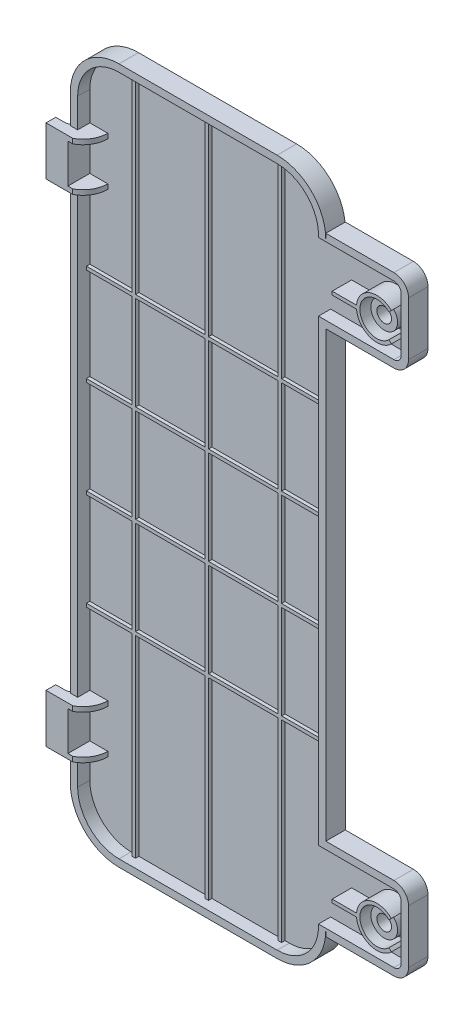
SolidWorks part; units mm, degrees
ref_plane "정면" through (0, 0, 0) normal (1, 0, 0) x (0, 1, 0)
ref_plane "윗면" through (0, 0, 0) normal (0, 0, 1) x (0, 1, 0)
ref_plane "우측면" through (0, 0, 0) normal (0, 1, 0) x (-1, 0, 0)
sketch "스케치1" plane through (0, 0, 0) normal (0, 0, 1) x (0, 1, 0)
  line L0 (-62.6, -26.25) -> (-62.6, -40.25)
  line L1 (-61.5, 26.25) -> (61.5, 26.25)
  line L2 (-71.5, 16.25) -> (-71.5, -16.25)
  line L3 (-61.5, -26.25) -> (-62.6, -26.25)
  line L4 (71.5, 16.25) -> (71.5, -16.25)
  line L5 (-71.5, 26.25) -> (0, 0) construction
  line L6 (-71.5, -26.25) -> (-48.7665, -17.9038) construction
  line L9 (-59.6, -43.25) -> (-48.6, -43.25)
  line L11 (-45.1107, -16.5616) -> (-40.2665, -26.25) construction
  line L12 (62.6, -26.25) -> (61.5, -26.25)
  line L15 (48.6, -43.25) -> (59.6, -43.25)
  line L17 (-45.6, -26.25) -> (45.6, -26.25)
  line L18 (0, 39.705) -> (0, -47.5697) construction
  line L19 (0, 0) -> (71.5, 26.25) construction
  line L20 (45.6, -26.25) -> (45.6, -40.25)
  line L21 (-45.6, -26.25) -> (-45.6, -40.25)
  line L24 (62.6, -26.25) -> (62.6, -40.25)
  line L25 (67.0036, -24.5992) -> (71.5, -26.25) construction
  arc A0 (61.5, 26.25) -> (71.5, 16.25) centre (61.5, 16.25) cw
  arc A1 (61.5, -26.25) -> (71.5, -16.25) centre (61.5, -16.25) ccw
  arc A2 (-71.5, -16.25) -> (-61.5, -26.25) centre (-61.5, -16.25) ccw
  arc A3 (-61.5, 26.25) -> (-71.5, 16.25) centre (-61.5, 16.25) ccw
  arc A4 (59.6, -43.25) -> (62.6, -40.25) centre (59.6, -40.25) ccw
  arc A5 (45.6, -40.25) -> (48.6, -43.25) centre (48.6, -40.25) ccw
  arc A6 (-48.6, -43.25) -> (-45.6, -40.25) centre (-48.6, -40.25) ccw
  arc A7 (-62.6, -40.25) -> (-59.6, -43.25) centre (-59.6, -40.25) ccw
  point P0 (0, 0)
  point P18 (-40.2665, -26.25)
  point P23 (45.1042, -26.25)
  point P27 (62.6, -43.25)
  point P36 (45.6, -43.25)
  point P41 (-45.6, -43.25)
  point P44 (-62.6, -43.25)
  point P47 (-45.6, -33.25)
  dimension "D3" = 10
  dimension "D8" = 3
  dimension "D1" = 143
  dimension "D2" = 52.5
  dimension "D4" = 17
  dimension "D5" = 17
  dimension "D6" = 17
  dimension "D7" = 17
  dimension "D9" = 45.6
  dimension "D10" = 45.6
extrude "보스-돌출1" add sketch "스케치1" along normal blind 4
shell "쉘1" thickness 1.5 removed face at (22.0743, 0, 4)
sketch "스케치2" plane through (0, 0, 0) normal (0, 0, -1) x (1, 0, 0)
  line L0 (43.25, 59.6) -> (43.25, 48.6) construction
  line L1 (43.25, -48.6) -> (43.25, -59.6) construction
  line L2 (26.25, 62.6) -> (40.25, 62.6) construction
  line L3 (40.25, -62.6) -> (26.25, -62.6) construction
  circle A0 centre (38.25, 54.1) radius 2.75
  circle A1 centre (38.25, -54.1) radius 2.75
  circle A2 centre (38.25, 54.1) radius 1.5
  circle A3 centre (38.25, -54.1) radius 1.5
  dimension "D1" = 5.5
  dimension "D2" = 5.5
  dimension "D3" = 5
  dimension "D4" = 5
  dimension "D5" = 8.5
  dimension "D6" = 8.5
extrude "보스-돌출2" add sketch "스케치2" against normal blind 4 contours A1 A3 | A0 A2 region at (35.5778, -54.1, 0) region at (35.5778, 54.1, 0)
sketch "스케치3" plane through (0, 0, 4) normal (0, 0, 1) x (1, 0, 0)
  line L1 (-24.75, 55.5) -> (-29.25, 55.5)
  line L2 (-24.75, 55.5) -> (-24.75, 45.5)
  line L3 (-24.75, 45.5) -> (-29.25, 45.5)
  line L4 (-29.25, 55.5) -> (-29.25, 45.5)
  line L6 (-24.75, -45.5) -> (-29.25, -45.5)
  line L7 (-24.75, -45.5) -> (-24.75, -55.5)
  line L8 (-24.75, -55.5) -> (-29.25, -55.5)
  line L9 (-29.25, -45.5) -> (-29.25, -55.5)
  line L11 (-24.75, 61.5) -> (-24.75, -61.5) construction
  line L12 (16.25, 71.5) -> (-16.25, 71.5) construction
  line L13 (-16.25, -71.5) -> (16.25, -71.5) construction
  point P10 (-27, -45.5)
  dimension "D1" = 10
  dimension "D2" = 10
  dimension "D3" = 4.5
  dimension "D4" = 4.5
  dimension "D5" = 0
  dimension "D6" = 0
  dimension "D7" = 91
  dimension "D8" = 143
  dimension "D9" = 16
extrude "보스-돌출3" add sketch "스케치3" along normal blind 2
fillet "필렛1" radius 1 2 edges at (-26.25, -50.5, 4) (-26.25, 50.5, 4)
sketch "스케치4" plane through (0, 0, 6) normal (0, 0, 1) x (1, 0, 0)
  line L1 (-24.75, 55.5) -> (-21.05, 55.5)
  line L2 (-24.75, 55.5) -> (-24.75, 54.5)
  line L3 (-24.75, 54.5) -> (-21.05, 54.5)
  line L4 (-21.05, 55.5) -> (-21.05, 54.5)
  line L5 (-24.75, 45.5) -> (-21.05, 45.5)
  line L6 (-24.75, 45.5) -> (-24.75, 46.5)
  line L7 (-24.75, 46.5) -> (-21.05, 46.5)
  line L8 (-21.05, 45.5) -> (-21.05, 46.5)
  line L9 (-24.75, -45.5) -> (-21.05, -45.5)
  line L10 (-24.75, -45.5) -> (-24.75, -46.5)
  line L11 (-24.75, -46.5) -> (-21.05, -46.5)
  line L12 (-21.05, -45.5) -> (-21.05, -46.5)
  line L13 (-24.75, -55.5) -> (-21.05, -55.5)
  line L14 (-24.75, -55.5) -> (-24.75, -54.5)
  line L15 (-24.75, -54.5) -> (-21.05, -54.5)
  line L16 (-21.05, -55.5) -> (-21.05, -54.5)
  dimension "D1" = 1
  dimension "D2" = 1
  dimension "D3" = 1
  dimension "D4" = 1
  dimension "D5" = 3.7
  dimension "D6" = 3.7
  dimension "D7" = 3.7
  dimension "D8" = 3.7
extrude "보스-돌출4" add sketch "스케치4" against normal up to surface (4.5 mm away) up to face at (35.5, 54.1, 1.5)
sketch "스케치5" plane through (0, -55.5, 0) normal (0, -1, 0) x (1, 0, 0)
  line L8 (-29.25, 4) -> (-27.25, 4)
  line L9 (-26.25, 3) -> (-26.25, 4)
  line L10 (-26.25, 4) -> (-24.75, 4)
  line L11 (-24.75, 4) -> (-24.75, 1.5)
  line L12 (-24.75, 1.5) -> (-21.05, 1.5)
  line L13 (-21.05, 1.5) -> (-21.05, 6)
  line L14 (-21.05, 6) -> (-29.25, 6)
  line L15 (-29.25, 6) -> (-29.25, 4)
  line L21 (-21.05, 1.5) -> (-21.05, 6)
  line L22 (-21.05, 6) -> (-23.7578, 6)
  arc A0 (-21.05, 1.5) -> (-23.7578, 6) centre (-26.1431, 1.5) ccw
  arc A1 (-26.25, 3) -> (-27.25, 4) centre (-27.25, 3) ccw
  dimension "D1" = 0
extrude "컷-돌출1" cut sketch "스케치5" against normal up to surface (111 mm away) up to face at (-25.5159, 55.5, 3.8008)
sketch "스케치6" plane through (0, 0, 1.5) normal (0, 0, 1) x (1, 0, 0)
  line L0 (0, -84.3384) -> (0, 78.6384) construction
  line L1 (-36.5942, 0) -> (41.0942, 0) construction
  line L2 (-16.25, -70) -> (16.25, -70) construction
  line L3 (-0.35, 70) -> (0.35, 70)
  line L4 (-0.35, 70) -> (-0.35, -70)
  line L5 (-0.35, -70) -> (0.35, -70)
  line L6 (0.35, 70) -> (0.35, -70)
  line L7 (-0.35, 70) -> (0.35, -70) construction
  line L8 (-0.35, -70) -> (0.35, 70) construction
  line L9 (14.65, 70) -> (14.65, -70)
  line L10 (14.65, 70) -> (15.35, 70)
  line L11 (15.35, 70) -> (15.35, -70)
  line L12 (14.65, -70) -> (15.35, -70)
  line L13 (-15.35, 70) -> (-15.35, -70)
  line L14 (-14.65, 70) -> (-14.65, -70)
  line L15 (-15.35, 70) -> (-14.65, 70)
  line L16 (-15.35, -70) -> (-14.65, -70)
  line L17 (24.75, -47.1) -> (24.75, 47.1) construction
  line L18 (-24.75, 9.65) -> (24.75, 9.65)
  line L19 (-24.75, 9.65) -> (-24.75, 10.35)
  line L20 (-24.75, 10.35) -> (24.75, 10.35)
  line L21 (24.75, 9.65) -> (24.75, 10.35)
  line L22 (-24.75, 9.65) -> (24.75, 10.35) construction
  line L23 (-24.75, 10.35) -> (24.75, 9.65) construction
  line L24 (-24.75, 30.35) -> (24.75, 30.35)
  line L25 (-24.75, 29.65) -> (24.75, 29.65)
  line L26 (-24.75, 29.65) -> (-24.75, 30.35)
  line L27 (24.75, 29.65) -> (24.75, 30.35)
  line L28 (24.75, -29.65) -> (24.75, -30.35)
  line L29 (24.75, -9.65) -> (24.75, -10.35)
  line L30 (-24.75, -9.65) -> (-24.75, -10.35)
  line L31 (-24.75, -29.65) -> (-24.75, -30.35)
  line L32 (-24.75, -30.35) -> (24.75, -30.35)
  line L33 (-24.75, -29.65) -> (24.75, -29.65)
  line L34 (-24.75, -10.35) -> (24.75, -10.35)
  line L35 (-24.75, -9.65) -> (24.75, -9.65)
  point P5 (0, 0)
  point P13 (0, 10)
  line M22 (-24.75, 45.5) -> (-24.75, -45.5)
  line M32 (-16.25, -70) -> (16.25, -70)
  line M40 (24.75, -47.1) -> (24.75, 47.1)
  line M48 (16.25, 70) -> (-16.25, 70)
  dimension "D1" = 0.7
  dimension "D4" = 0.7
  dimension "D5" = 10
  dimension "D2" = 2
  dimension "D3" = 2
  dimension "D6" = 2
extrude "보스-돌출9" add sketch "스케치6" along normal blind 0.7 contours L32 L13 L14 M32 | L35 L6 L34 L9 | L35 L11 L34 M40 | L35 L14 L34 L4 | L11 L25 L24 M40 | L6 L25 L9 L24 | L9 L25 L11 L24 | L25 L9 L20 L11 | L9 L24 L11 M48 | L14 L25 L4 L24 | L25 L4 L20 L6 | L4 L25 L6 L24 | L4 L24 L6 M48 | L25 L13 L24 M22 | L13 L24 L14 M48 | L13 L25 L14 L24 | L25 L13 L20 L14 | L20 L18 L13 M22 | L13 L35 L14 L18 | L20 L13 L18 L14 | L20 L14 L18 L4 | L4 L35 L6 L18 | L20 L6 L18 L9 | L20 L4 L18 L6 | L20 L11 L18 M40 | L20 L9 L18 L11 | L9 L35 L11 L18 | L35 L9 L34 L11 | L34 L9 L33 L11 | L33 L6 L32 L9 | L33 L14 L32 L4 | L33 L4 L32 L6 | L34 L4 L33 L6 | L32 L4 L6 M32 | L35 L4 L34 L6 | L33 L32 L13 M22 | L33 L13 L32 L14 | L34 L13 L33 L14 | L33 L9 L32 L11 | L32 L9 L11 M32 | L33 L11 L32 M40 | L35 L34 L13 M22 | L35 L13 L34 L14 | L11 L12 L9 L10 | L32 L28 L33 L31 | L6 L5 L4 L3 | L13 L16 L14 L15 | L34 L29 L35 L30 region at (0, 50.175, 1.5) region at (0, 30, 1.5) region at (-7.5, 30, 1.5) region at (-15, 50.175, 1.5) region at (7.5, 30, 1.5) region at (15, 50.175, 1.5) region at (0, 20, 1.5) region at (-15, 30, 1.5) region at (15, 30, 1.5) region at (0, 10, 1.5) region at (-7.5, 10, 1.5) region at (-15, 20, 1.5) region at (-20.05, 30, 1.5) region at (7.5, 10, 1.5) region at (15, 20, 1.5) region at (20.05, 30, 1.5) region at (0, 0, 1.5) region at (-15, 10, 1.5) region at (15, 10, 1.5) region at (0, -10, 1.5) region at (-7.5, -10, 1.5) region at (-15, 0, 1.5) region at (-20.05, 10, 1.5) region at (7.5, -10, 1.5) region at (15, 0, 1.5) region at (20.05, 10, 1.5) region at (0, -20, 1.5) region at (-15, -10, 1.5) region at (15, -10, 1.5) region at (0, -30, 1.5) region at (-7.5, -30, 1.5) region at (-15, -20, 1.5) region at (-20.05, -10, 1.5) region at (7.5, -30, 1.5) region at (15, -20, 1.5) region at (20.05, -10, 1.5) region at (0, -50.175, 1.5) region at (-15, -30, 1.5) region at (15, -30, 1.5) region at (-15, -50.175, 1.5) region at (-20.05, -30, 1.5) region at (15, -50.175, 1.5) region at (20.05, -30, 1.5)
sketch "스케치7" plane through (0, 0, 0) normal (0, 0, -1) x (1, 0, 0)
  circle A0 centre (38.25, 54.1) radius 2.75
  circle A1 centre (38.25, -54.1) radius 2.75
extrude "컷-돌출2" cut sketch "스케치7" against normal blind 1.5
sketch "스케치9" plane through (0, 0, 4) normal (0, 0, 1) x (1, 0, 0)
  line L0 (38.25, 54.1) -> (46.7333, 54.1) construction
  line L1 (40.7249, 56.5749) -> (41.2198, 57.0698)
  line L2 (40.7249, 51.6251) -> (41.2198, 51.1302)
  line L3 (0, 0) -> (61.292, 0) construction
  line L4 (29.0646, 54.45) -> (34.0646, 54.45)
  line L5 (29.0646, 54.45) -> (29.0646, 53.75)
  line L6 (29.0646, 53.75) -> (34.0646, 53.75)
  line L8 (29.0646, 54.45) -> (41.8601, 53.5863) construction
  line L9 (29.0646, 53.75) -> (34.25, 54.1) construction
  line L10 (29.0646, -53.75) -> (34.25, -54.1) construction
  line L11 (29.0646, -54.45) -> (41.8601, -53.5863) construction
  line L12 (38.25, -54.1) -> (46.7333, -54.1) construction
  line L13 (29.0646, -53.75) -> (34.0646, -53.75)
  line L14 (29.0646, -54.45) -> (29.0646, -53.75)
  line L15 (29.0646, -54.45) -> (34.0646, -54.45)
  line L16 (40.7249, -51.6251) -> (41.2198, -51.1302)
  line L17 (40.7249, -56.5749) -> (41.2198, -57.0698)
  arc A0 (40.7249, 56.5749) -> (40.7249, 51.6251) centre (38.25, 54.1) ccw
  arc A1 (41.2198, 57.0698) -> (34.0646, 54.45) centre (38.25, 54.1) ccw
  circle A2 centre (38.25, 54.1) radius 4.2 construction
  circle A3 centre (38.25, 54.1) radius 3.5 construction
  arc A4 (34.0646, 53.75) -> (41.2198, 51.1302) centre (38.25, 54.1) ccw
  arc A5 (34.0646, -53.75) -> (41.2198, -51.1302) centre (38.25, -54.1) cw
  arc A6 (41.2198, -57.0698) -> (34.0646, -54.45) centre (38.25, -54.1) cw
  arc A7 (40.7249, -56.5749) -> (40.7249, -51.6251) centre (38.25, -54.1) cw
  point P1 (34.25, 54.1)
  point P32 (34.25, -54.1)
  dimension "D1" = 7
  dimension "D3" = 45
  dimension "D4" = 45
  dimension "D5" = 0.7
  dimension "D6" = 4
  dimension "D7" = 5
  dimension "D8" = 0
  dimension "D2" = 0.7
extrude "보스-돌출11" add sketch "스케치9" along normal blind 1.5 and the other way up to surface (2.5 mm away) separate body other way up to face at (35.5, -54.1, 1.5)
